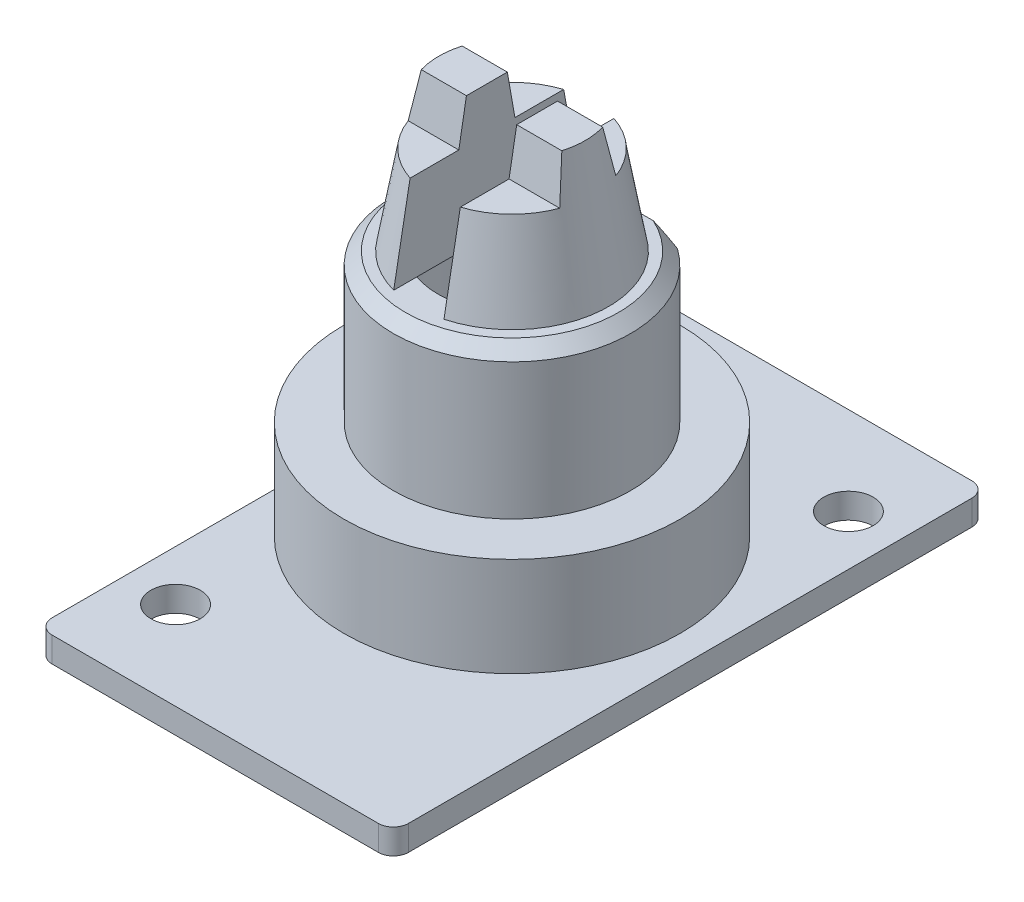
SolidWorks part; units mm, degrees
ref_plane "Front Plane" through (0, 0, 0) normal (0, 0, 1) x (1, 0, 0)
ref_plane "Top Plane" through (0, 0, 0) normal (0, 1, 0) x (1, 0, 0)
ref_plane "Right Plane" through (0, 0, 0) normal (1, 0, 0) x (0, 0, -1)
ref_plane "Plane1" through (0, 0, 0) normal (0, 1, 0) x (1, 0, 0)
sketch "Sketch1" plane through (0, 0, 0) normal (0, 1, 0) x (1, 0, 0)
  line L0 (-9.0043, 14.2367) -> (-9.0043, -14.2367)
  line L1 (-8.2423, -14.9987) -> (8.2423, -14.9987)
  line L2 (9.0043, -14.2367) -> (9.0043, 14.2367)
  line L3 (8.2423, 14.9987) -> (-8.2423, 14.9987)
  arc A0 (-9.0043, -14.2367) -> (-8.2423, -14.9987) centre (-8.2423, -14.2367) ccw
  arc A1 (8.2423, -14.9987) -> (9.0043, -14.2367) centre (8.2423, -14.2367) ccw
  arc A2 (9.0043, 14.2367) -> (8.2423, 14.9987) centre (8.2423, 14.2367) ccw
  arc A3 (-8.2423, 14.9987) -> (-9.0043, 14.2367) centre (-8.2423, 14.2367) ccw
extrude "Boss-Extrude1" add sketch "Sketch1" along normal blind 1.27
ref_plane "Plane2" through (0, 0, 0) normal (1, 0, 0) x (0, 0, -1)
sketch "Sketch2" plane through (0, 0, 0) normal (1, 0, 0) x (0, 0, -1)
  line L0 (3.7592, 14.7066) -> (3.7592, 0.9398)
  line L1 (3.7592, 0.9398) -> (6.5892, 0.9398)
  line L2 (6.5892, 0.9398) -> (6.127, 2.2098)
  line L3 (6.127, 2.2098) -> (8.4963, 2.2098)
  line L4 (8.4963, 2.2098) -> (8.4963, 7.2136)
  line L5 (8.4963, 7.2136) -> (6, 7.2136)
  line L6 (6, 7.2136) -> (6, 14.0931)
  line L7 (6, 14.0931) -> (5.3865, 14.7066)
  line L8 (5.3865, 14.7066) -> (3.7592, 14.7066)
  line L9 (0, 0.9398) -> (0, 14.7066) construction
revolve "Revolve1" add sketch "Sketch2" angle 360 about L9 reverse direction yes
cosmetic thread "Cosmetic Thread1" parameters "D1"=6.985, "D2"=10.773
ref_plane "Plane3" through (0, 14.7066, 0) normal (0, 1, 0) x (1, 0, 0)
sketch "Sketch3" plane through (0, 14.7066, 0) normal (0, 1, 0) x (1, 0, 0)
  line L0 (-6, 4.8966) -> (6, 4.8966)
  line L1 (6, 4.8966) -> (6, 16.8966)
  line L2 (6, 16.8966) -> (-6, 16.8966)
  line L3 (-6, 16.8966) -> (-6, 4.8966)
extrude "Cut-Extrude1" cut sketch "Sketch3" against normal blind 6.985 and the other way blind 6.985
ref_plane "Plane4" through (0, 0, 0) normal (1, 0, 0) x (0, 0, -1)
sketch "Sketch4" plane through (0, 0, 0) normal (1, 0, 0) x (0, 0, -1)
  line L0 (0, 22.098) -> (3.5735, 22.098)
  line L1 (3.5735, 22.098) -> (4.8768, 14.7066)
  line L2 (4.8768, 14.7066) -> (0, 14.7066)
  line L3 (0, 14.7066) -> (0, 22.098)
  line L4 (0, 14.7066) -> (0, 22.098) construction
revolve "Revolve2" add sketch "Sketch4" angle 360 about L4 reverse direction yes
ref_plane "Plane5" through (0, 0, 0) normal (1, 0, 0) x (0, 0, -1)
sketch "Sketch5" plane through (0, 0, 0) normal (1, 0, 0) x (0, 0, -1)
  line L0 (-4.8768, 23.6982) -> (-4.0841, 19.2024)
  line L1 (-4.0841, 19.2024) -> (-1.4181, 19.2024)
  line L2 (-1.4181, 19.2024) -> (-1.033, 21.3868)
  line L3 (-1.033, 21.3868) -> (1.033, 21.3868)
  line L4 (1.033, 21.3868) -> (1.4181, 19.2024)
  line L5 (1.4181, 19.2024) -> (4.0841, 19.2024)
  line L6 (4.0841, 19.2024) -> (4.8768, 23.6982)
  line L7 (4.8768, 23.6982) -> (-4.8768, 23.6982)
extrude "Cut-Extrude2" cut sketch "Sketch5" against normal blind 12 and the other way blind 12
ref_plane "Plane6" through (0, 0, 0) normal (1, 0, 0) x (0, 0, -1)
sketch "Sketch6" plane through (0, 0, 0) normal (1, 0, 0) x (0, 0, -1)
  line L0 (-4.8768, 14.7066) -> (4.8768, 14.7066)
  line L1 (4.8768, 14.7066) -> (4.8768, 22.098)
  line L2 (4.8768, 22.098) -> (-4.8768, 22.098)
  line L3 (-4.8768, 22.098) -> (-4.8768, 14.7066)
extrude "Cut-Extrude3" cut sketch "Sketch6" against normal blind 1.27 and the other way blind 1.27
ref_plane "Plane7" through (0, 0, 0) normal (0, 1, 0) x (1, 0, 0)
sketch "Sketch7" plane through (0, 0, 0) normal (0, 1, 0) x (1, 0, 0)
  circle A0 centre (6.4643, 10.541) radius 1.25
extrude "Cut-Extrude4" cut sketch "Sketch7" against normal blind 2.54 and the other way blind 2.54
ref_plane "Plane8" through (0, 0, 0) normal (0, 1, 0) x (1, 0, 0)
sketch "Sketch8" plane through (0, 0, 0) normal (0, 1, 0) x (1, 0, 0)
  circle A0 centre (-6.4643, -10.541) radius 1.25
extrude "Cut-Extrude5" cut sketch "Sketch8" against normal blind 2.54 and the other way blind 2.54
